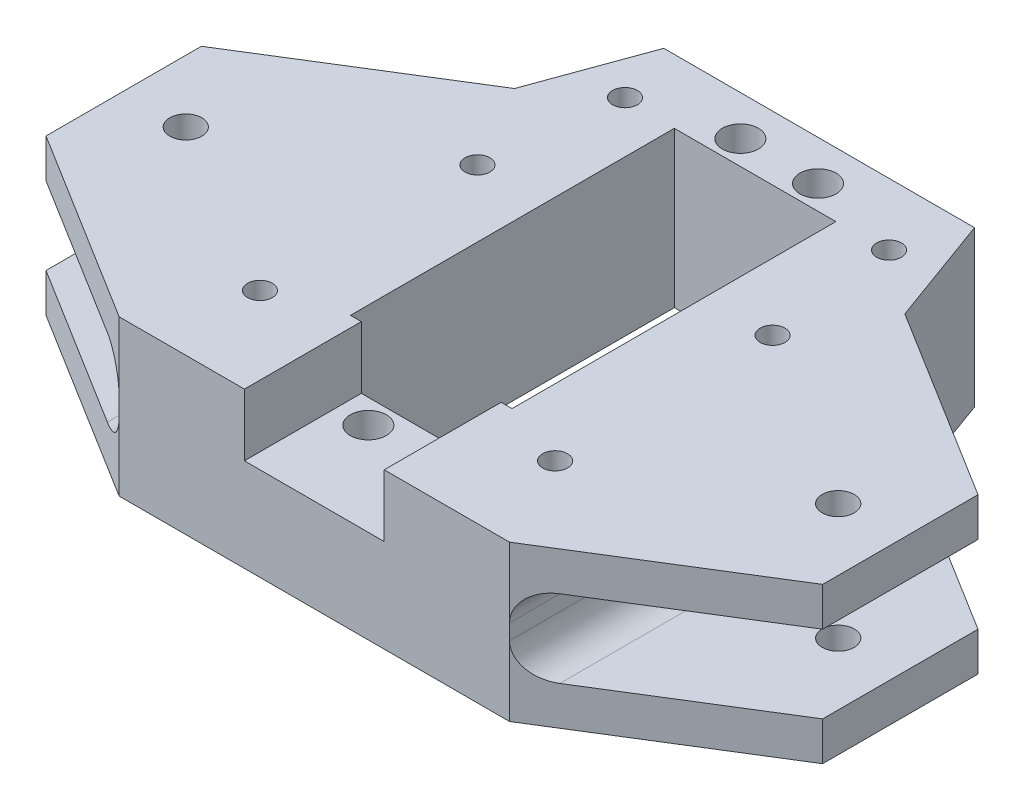
SolidWorks part; units mm, degrees
ref_plane "Front Plane" through (0, 0, 0) normal (0, 0, 1) x (1, 0, 0)
ref_plane "Top Plane" through (0, 0, 0) normal (0, 1, 0) x (1, 0, 0)
ref_plane "Right Plane" through (0, 0, 0) normal (1, 0, 0) x (0, 0, -1)
sketch "Sketch1" plane through (0, 0, 0) normal (0, 1, 0) x (1, 0, 0)
  line L0 (0, 0) -> (0, 55585.7092) construction
  line L1 (0, 0) -> (55585.7092, 0) construction
  line L2 (20, 39.5477) -> (-20, 39.5477)
  line L3 (-20, 39.5477) -> (-25.1303, 25.4523)
  line L4 (-25.1303, 25.4523) -> (-50, 10)
  line L5 (-50, 10) -> (-50, -10)
  line L11 (50, 10) -> (50, -10)
  line L12 (25.1303, 25.4523) -> (50, 10)
  line L13 (20, 39.5477) -> (25.1303, 25.4523)
  line L14 (25.1303, -25.4523) -> (50, -10)
  line L15 (-25.1303, -25.4523) -> (-50, -10)
  line L19 (25.1303, -25.4523) -> (-25.1303, -25.4523)
  point P7 (50, 0)
  point P12 (-50, 0)
  point P14 (0, -10.7407)
  point P19 (0, 39.5477)
  dimension "D1" = 40
  dimension "D2" = 20
  dimension "D3" = 65
  dimension "D4" = 100
  dimension "D5" = 110
  dimension "D8" = 15
extrude "Main-Body" add sketch "Sketch1" along normal mid plane 20
sketch "Sketch2" plane through (0, 10, 0) normal (0, 1, 0) x (1, 0, 0)
  line L0 (0, 47.5477) -> (0, -49952.4523) construction
  line L1 (-50, 0) -> (49950, 0) construction
  line L2 (20, 39.5477) -> (-20, 39.5477) construction
  line L3 (-10, 10.45) -> (10, 10.45) construction
  line L4 (10, -10) -> (-10, -10) construction
  line L5 (-10, -10) -> (-10, 30.9) construction
  line L6 (-10, 30.9) -> (10, 30.9) construction
  line L7 (10, -10) -> (10, 30.9) construction
  line L8 (0, -25.4523) -> (50000, -25.4523) construction
  line L9 (-50, 10) -> (-50, -10) construction
  line L10 (-5, 34.4) -> (5, 34.4) construction
  line L11 (-5, -13.5) -> (5, -13.5) construction
  line L12 (-25.1303, -25.4523) -> (25.1303, -25.4523) construction
  line L14 (-10.4, 31.3) -> (10.4, 31.3)
  line L15 (-10.4, 31.3) -> (-10.4, -10.4)
  line L16 (-10.4, -10.4) -> (10.4, -10.4)
  line L17 (10.4, 31.3) -> (10.4, -10.4)
  line L18 (-10.4, 31.3) -> (10.4, -10.4) construction
  line L19 (-10.4, -10.4) -> (10.4, 31.3) construction
  circle A0 centre (-5, -13.5) radius 2.325
  circle A1 centre (5, -13.5) radius 2.325
  circle A2 centre (-5, 34.4) radius 2.325
  circle A3 centre (5, 34.4) radius 2.325
  circle A4 centre (0, 0) radius 2 construction
  circle A5 centre (-42, 0) radius 2.0625
  circle A6 centre (42, 0) radius 2.0625
  point P22 (0, -10)
  point P23 (0, 30.9)
  point P28 (0, 39.5477)
  point P29 (0, -13.5)
  point P30 (0, 34.4)
  point P31 (-50, 0)
  point P32 (0, 10.45)
  dimension "D1" = 4.65
  dimension "D4" = 4.65
  dimension "D10" = 4.65
  dimension "D11" = 4.65
  dimension "D13" = 4
  dimension "D16" = 4.125
  dimension "D3" = 10
  dimension "D6" = 10
  dimension "D7" = 20
  dimension "D8" = 3.5
  dimension "D9" = 3.5
  dimension "D5" = 40.9
  dimension "D2" = 0.4
  dimension "D12" = 0.4
  dimension "D14" = 10
  dimension "D15" = 0
  dimension "D17" = 8
extrude "Servo&RotRod-Cutout" cut sketch "Sketch2" against normal blind 30
sketch "Sketch3" plane through (0, 0, 25.4523) normal (0, 0, 1) x (1, 0, 0)
  line L0 (0, 0) -> (0, 50000) construction
  line L1 (0, 0) -> (48695.3801, 0) construction
  line L3 (9, 10) -> (-9, 10)
  line L4 (-9, 10) -> (-9, 2)
  line L5 (-9, 2) -> (9, 2)
  line L6 (9, 10) -> (9, 2)
  line L7 (-25.1303, 10) -> (25.1303, 10) construction
  point P10 (0, 0)
  point P11 (0, 10)
  dimension "D1" = 18
  dimension "D2" = 8
  dimension "D3" = 0
extrude "Servo-Cable-Cutout" cut sketch "Sketch3" against normal up to surface (15.0523 mm away) up to face at (0, 0, 10.4)
sketch "Sketch4" plane through (0, 0, 25.4523) normal (0, 0, 1) x (1, 0, 0)
  line L0 (0, 0) -> (0, 50000) construction
  line L1 (50, 0) -> (50050, 0) construction
  line L2 (50, 10) -> (50, -10) construction
  line L3 (-50, -5) -> (-50, 5)
  line L4 (-50, 10) -> (-50, -10) construction
  line L5 (-50, 5) -> (-25.1303, 5)
  line L6 (-25.1303, 5) -> (-25.1303, -5)
  line L7 (-50, -5) -> (-25.1303, -5)
  line L10 (-25.1303, 10) -> (-25.1303, -10) construction
  point P7 (50, 0)
  point P15 (-25.1303, 0)
  point P16 (-50, 0)
  dimension "D1" = 0
  dimension "D2" = 10
extrude "Control-Arm-Cutout" cut sketch "Sketch4" against normal through all both and the other way through all
mirror "Mirror1" about plane through (0, 0, 0) normal (1, 0, 0) of "Control-Arm-Cutout"
sketch "Sketch5" plane through (0, 10, 0) normal (0, 1, 0) x (1, 0, 0)
  line L0 (-50, 0) -> (49950, 0) construction
  line L1 (-50, 10) -> (-50, -10) construction
  line L2 (0, 0) -> (0, 50000) construction
  circle A0 centre (-40, 0) radius 2.05
  point P4 (-50, 0)
  dimension "D1" = 4.1
  dimension "D2" = 10
extrude "Cut-Extrude4" [suppressed] cut sketch "Sketch5" against normal through all both and the other way through all
mirror "Mirror2" [suppressed] about plane through (0, 0, 0) normal (1, 0, 0)
fillet "Fillet1" radius 4 4 edges at (-25.1303, -5, 0) (-25.1303, 5, 0) (25.1303, -5, 0) (25.1303, 5, 0)
sketch "Sketch6" plane through (0, -10, 0) normal (0, -1, 0) x (1, 0, 0)
  line L0 (0, 0) -> (0, -50000) construction
  line L1 (19, -12.4414) -> (19, -50012.4414) construction
  line L2 (-25.1303, 25.4523) -> (25.1303, 25.4523) construction
  line L3 (20, -39.5477) -> (-20, -39.5477) construction
  circle A0 centre (19, -14.5477) radius 1.6
  circle A1 centre (19, 13.4523) radius 1.6
  circle A2 centre (17, -31.5477) radius 1.6
  circle A3 centre (-17, -31.5477) radius 1.6
  circle A4 centre (-19, 13.4523) radius 1.6
  circle A5 centre (-19, -14.5477) radius 1.6
  dimension "D2" = 3.2
  dimension "D3" = 3.2
  dimension "D7" = 3.2
  dimension "D1" = 19
  dimension "D4" = 12
  dimension "D5" = 25
  dimension "D6" = 17
  dimension "D8" = 8
extrude "Mount-Holes-Chassis" cut sketch "Sketch6" against normal through all
sketch "Sketch7" plane through (0, -10, 0) normal (0, -1, 0) x (1, 0, 0)
  line L0 (0, 0) -> (0, -50000) construction
  circle A0 centre (17, -31.5477) radius 3.25
  circle A1 centre (19, -14.5477) radius 3.25
  circle A2 centre (19, 13.4523) radius 3.25
  circle A3 centre (-19, 13.4523) radius 3.25
  circle A4 centre (-19, -14.5477) radius 3.25
  circle A5 centre (-17, -31.5477) radius 3.25
  dimension "D1" = 6.5
  dimension "D2" = 6.5
  dimension "D3" = 6.5
extrude "Bolt-Head-Holes" cut sketch "Sketch7" against normal blind 4.5
equation "\"D10@Sketch2\"=\"D1@Sketch2\""
equation "\"D11@Sketch2\"=\"D1@Sketch2\""
equation "\"D3@Sketch6\"=\"D2@Sketch6\""
equation "\"D7@Sketch6\"=\"D2@Sketch6\""
equation "\"D2@Sketch7\"=\"D1@Sketch7\""
equation "\"D3@Sketch7\"=\"D1@Sketch7\""
